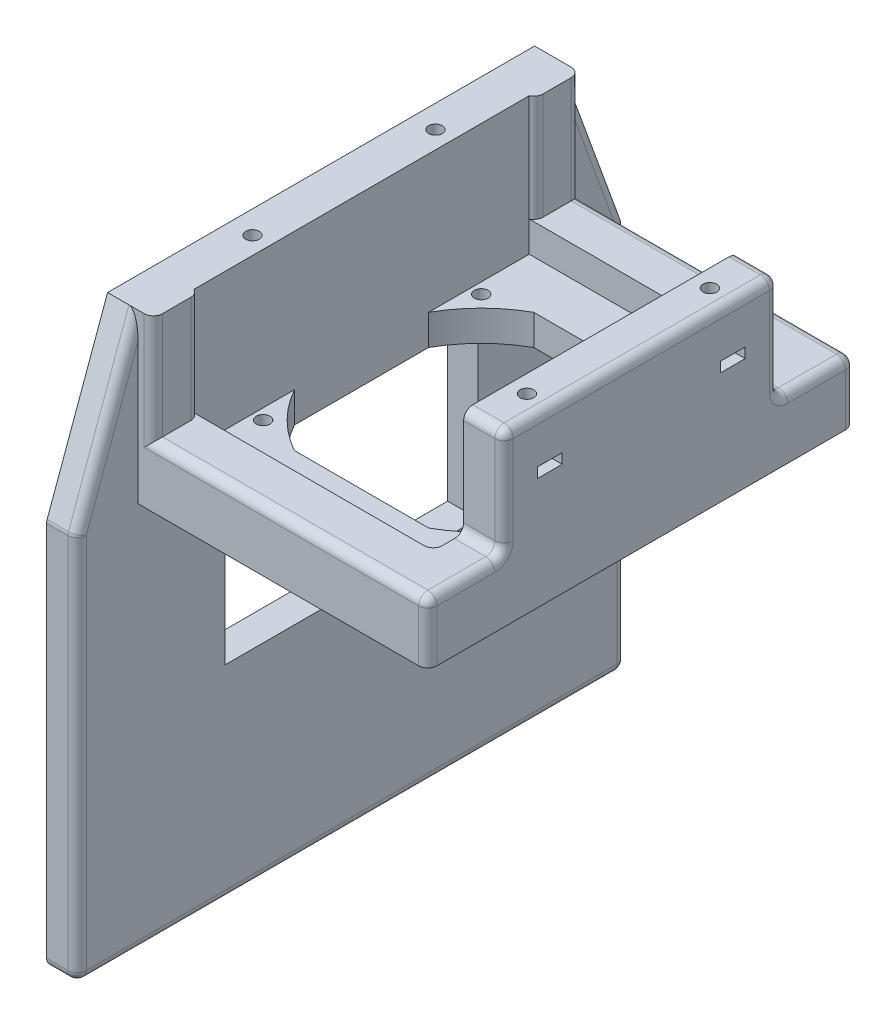
SolidWorks part; units mm, degrees
ref_plane "Front Plane" through (0, 0, 0) normal (0, 0, 1) x (1, 0, 0)
ref_plane "Top Plane" through (0, 0, 0) normal (0, 1, 0) x (1, 0, 0)
ref_plane "Right Plane" through (0, 0, 0) normal (1, 0, 0) x (0, 0, -1)
sketch "Sketch1" plane through (0, 0, 0) normal (0, 1, 0) x (1, 0, 0)
  line L9 (0, 0) -> (190, 0)
  line L10 (0, 0) -> (0, 140)
  line L11 (0, 140) -> (190, 140)
  line L12 (190, 0) -> (190, 140)
  dimension "D1" = 190
  dimension "D2" = 140
extrude "Boss-Extrude1" add sketch "Sketch1" along normal blind 10
sketch "Sketch3" plane through (0, 10, 0) normal (0, 1, 0) x (1, 0, 0)
  line L1 (42.5, 25) -> (57.5, 25)
  line L2 (42.5, 25) -> (42.5, 115)
  line L3 (42.5, 115) -> (57.5, 115)
  line L4 (57.5, 25) -> (57.5, 115)
  line L5 (42.5, 25) -> (57.5, 115) construction
  line L6 (42.5, 115) -> (57.5, 25) construction
  line L7 (0, 70) -> (190, 70) construction
  line L8 (0, 140) -> (0, 0) construction
  line L9 (190, 0) -> (190, 140) construction
  line L10 (95, 140) -> (95, 0) construction
  line L11 (190, 140) -> (0, 140) construction
  line L12 (0, 0) -> (190, 0) construction
  line L13 (147.5, 115) -> (132.5, 115)
  line L14 (132.5, 25) -> (132.5, 115)
  line L15 (147.5, 25) -> (132.5, 25)
  line L16 (147.5, 25) -> (147.5, 115)
  line L17 (132.5, 115) -> (147.5, 25) construction
  line L18 (147.5, 115) -> (132.5, 25) construction
  point P0 (50, 70)
  dimension "D1" = 45
  dimension "D2" = 75
  dimension "D3" = 90
extrude "Boss-Extrude3" add sketch "Sketch3" along normal blind 35
sketch "Sketch4" plane through (0, 45, 0) normal (0, 1, 0) x (1, 0, 0)
  line L0 (42.5, 70) -> (147.5, 70) construction
  line L1 (42.5, 115) -> (42.5, 25) construction
  line L2 (147.5, 25) -> (147.5, 115) construction
  line L3 (50, 100) -> (50, 70) construction
  line L4 (50, 115) -> (50, 100) construction
  line L5 (57.5, 115) -> (42.5, 115) construction
  circle A0 centre (50, 100) radius 2.25
  circle A1 centre (140, 100) radius 2.25
  circle A2 centre (140, 40) radius 2.25
  circle A3 centre (50, 40) radius 2.25
  dimension "D1" = 4.5
  dimension "D4" = 30
  dimension "D2" = 2
  dimension "D3" = 2
extrude "Cut-Extrude1" cut sketch "Sketch4" against normal blind 20
sketch "Sketch5" plane through (0, 10, 0) normal (0, 1, 0) x (1, 0, 0)
  line L0 (57.5, 25) -> (57.5, 115) construction
  line L1 (57.5, 125) -> (132.5, 125)
  line L2 (57.5, 125) -> (57.5, 15)
  line L3 (57.5, 15) -> (132.5, 15)
  line L4 (132.5, 125) -> (132.5, 15)
  line L5 (132.5, 115) -> (132.5, 25) construction
  line L6 (57.5, 25) -> (57.5, 115) construction
  line L8 (57.5, 70) -> (42.5, 70) construction
  line L10 (42.5, 115) -> (42.5, 25) construction
  dimension "D1" = 110
extrude "Cut-Extrude2" cut sketch "Sketch5" against normal blind 50
sketch "Sketch6" plane through (0, 0, 0) normal (0, -1, 0) x (-1, 0, 0)
  circle A0 centre (-50, 40) radius 4.5
  circle A1 centre (-140, 40) radius 4.5
  circle A2 centre (-140, 100) radius 4.5
  circle A3 centre (-50, 100) radius 4.5
  dimension "D1" = 2
  dimension "D2" = 2
extrude "Cut-Extrude3" [suppressed] cut sketch "Sketch6" against normal blind 10
sketch "Sketch8" plane through (0, 10, 0) normal (0, 1, 0) x (1, 0, 0)
  line L0 (10, 130) -> (10, 140) construction
  line L1 (190, 140) -> (0, 140) construction
  line L2 (10, 130) -> (0, 130) construction
  line L3 (0, 140) -> (0, 0) construction
  line L4 (190, 0) -> (190, 140) construction
  line L5 (0, 0) -> (190, 0) construction
  circle A0 centre (10, 130) radius 2.5
  circle A1 centre (180, 130) radius 2.5
  circle A2 centre (180, 10) radius 2.5
  circle A3 centre (10, 10) radius 2.5
  dimension "D1" = 10
  dimension "D2" = 10
  dimension "D5" = 10
  dimension "D6" = 10
  dimension "D3" = 2
  dimension "D4" = 2
extrude "Cut-Extrude4" cut sketch "Sketch8" against normal blind 10 contours A0
ref_plane "Plane1" through (0, 30, 0) normal (0, 1, 0) x (1, 0, 0)
sketch "Sketch10" plane through (0, 30, 0) normal (0, 1, 0) x (1, 0, 0)
  line L0 (45.95, 44.05) -> (42.5, 44.05)
  line L1 (54.05, 35.95) -> (45.95, 35.95)
  line L2 (54.05, 35.95) -> (54.05, 44.05)
  line L3 (54.05, 44.05) -> (45.95, 44.05)
  line L5 (54.05, 35.95) -> (45.95, 44.05) construction
  line L6 (54.05, 44.05) -> (45.95, 35.95) construction
  line L7 (42.5, 115) -> (42.5, 25) construction
  line L8 (42.5, 44.05) -> (42.5, 35.95)
  line L9 (42.5, 35.95) -> (45.95, 35.95)
  line L10 (42.5, 95.95) -> (45.95, 95.95)
  line L11 (54.05, 95.95) -> (45.95, 95.95)
  line L12 (54.05, 95.95) -> (54.05, 104.05)
  line L13 (54.05, 104.05) -> (45.95, 104.05)
  line L14 (45.95, 104.05) -> (42.5, 104.05)
  line L15 (42.5, 104.05) -> (42.5, 95.95)
  line L19 (95, 125) -> (95, 29.9699) construction
  line L20 (135.95, 44.05) -> (144.05, 35.95) construction
  line L21 (135.95, 35.95) -> (144.05, 44.05) construction
  line L22 (147.5, 35.95) -> (144.05, 35.95)
  line L23 (147.5, 44.05) -> (147.5, 35.95)
  line L24 (135.95, 44.05) -> (144.05, 44.05)
  line L25 (135.95, 35.95) -> (135.95, 44.05)
  line L26 (135.95, 35.95) -> (144.05, 35.95)
  line L27 (144.05, 44.05) -> (147.5, 44.05)
  line L28 (147.5, 104.05) -> (147.5, 95.95)
  line L29 (144.05, 104.05) -> (147.5, 104.05)
  line L30 (135.95, 104.05) -> (144.05, 104.05)
  line L31 (135.95, 95.95) -> (135.95, 104.05)
  line L32 (135.95, 95.95) -> (144.05, 95.95)
  line L33 (147.5, 95.95) -> (144.05, 95.95)
  point P0 (50, 40)
  point P32 (140, 40)
  dimension "D1" = 8.1
  dimension "D2" = 8.1
  dimension "D3" = 2
extrude "Cut-Extrude5" cut sketch "Sketch10" against normal blind 3.3
sketch "Sketch11" plane through (0, 10, 0) normal (0, 1, 0) x (1, 0, 0)
  line L0 (190, 140) -> (0, 140) construction
  line L1 (147.5, 140) -> (190, 140)
  line L2 (147.5, 140) -> (147.5, 0)
  line L3 (147.5, 0) -> (190, 0)
  line L4 (190, 140) -> (190, 0)
  line L5 (147.5, 25) -> (147.5, 115) construction
  line L6 (95, 125) -> (95, 15) construction
  line L7 (132.5, 125) -> (57.5, 125) construction
  line L8 (57.5, 15) -> (132.5, 15) construction
  line L9 (42.5, 0) -> (0, 0)
  line L10 (0, 140) -> (0, 0)
  line L11 (42.5, 140) -> (0, 140)
  line L12 (42.5, 140) -> (42.5, 0)
  point P15 (95, 35)
extrude "Cut-Extrude6" cut sketch "Sketch11" against normal blind 10
sketch "Sketch12" plane through (0, 10, 0) normal (0, 1, 0) x (1, 0, 0)
  line L0 (42.5, 0) -> (147.5, 0) construction
  line L1 (42.5, 140) -> (57.5, 140)
  line L2 (42.5, 140) -> (42.5, 115)
  line L3 (42.5, 115) -> (57.5, 115)
  line L4 (57.5, 140) -> (57.5, 115)
  line L5 (42.5, 25) -> (57.5, 25)
  line L6 (42.5, 25) -> (42.5, 0)
  line L7 (42.5, 0) -> (57.5, 0)
  line L8 (57.5, 25) -> (57.5, 0)
extrude "Boss-Extrude4" add sketch "Sketch12" along normal up to surface (35 mm away) up to face at (50, 45, -37.75)
sketch "Sketch14" plane through (0, 0, 0) normal (0, -1, 0) x (1, 0, 0)
  line L4 (147.5, -140) -> (147.5, 0)
  line L5 (147.5, 0) -> (42.5, 0)
  line L6 (42.5, 0) -> (42.5, -140)
  line L7 (42.5, -140) -> (147.5, -140)
  line L8 (147.5, -140) -> (147.5, 0)
  line L9 (147.5, 0) -> (42.5, 0)
  line L10 (42.5, 0) -> (42.5, -140)
  line L11 (42.5, -140) -> (147.5, -140)
  dimension "D1" = 0
extrude "Boss-Extrude5" add sketch "Sketch14" along normal blind 10
sketch "Sketch15" plane through (0, -10, 0) normal (0, -1, 0) x (1, 0, 0)
  line L0 (59.25, -34.25) -> (130.75, -34.25) construction
  line L1 (130.75, -34.25) -> (130.75, -105.75) construction
  line L2 (59.25, -34.25) -> (59.25, -105.75) construction
  line L3 (59.25, -105.75) -> (130.75, -105.75) construction
  line L4 (95, 0) -> (95, -34.25) construction
  line L5 (147.5, 0) -> (42.5, 0) construction
  line L6 (42.5, -70) -> (59.25, -70) construction
  line L7 (42.5, 0) -> (42.5, -140) construction
  line L8 (59.25, -34.25) -> (130.75, -105.75) construction
  line L9 (130.75, -34.25) -> (59.25, -105.75) construction
  line L10 (72.9901, -30.75) -> (117.0099, -30.75)
  line L11 (134.25, -47.9901) -> (134.25, -92.0099)
  line L12 (72.9901, -109.25) -> (134.25, -109.25)
  line L13 (55.75, -47.9901) -> (55.75, -92.0099)
  line L14 (55.75, -30.75) -> (134.25, -30.75) construction
  line L15 (55.75, -30.75) -> (55.75, -109.25) construction
  line L16 (134.25, -30.75) -> (134.25, -109.25) construction
  line L17 (55.75, -109.25) -> (134.25, -109.25) construction
  arc A0 (72.9901, -30.75) -> (55.75, -47.9901) centre (95, -70) ccw
  circle A1 centre (59.25, -34.25) radius 2.25
  circle A2 centre (130.75, -34.25) radius 2.25
  circle A3 centre (130.75, -105.75) radius 2.25
  circle A4 centre (59.25, -105.75) radius 2.25
  arc A5 (134.25, -47.9901) -> (117.0099, -30.75) centre (95, -70) ccw
  arc A6 (117.0099, -109.25) -> (134.25, -92.0099) centre (95, -70) ccw
  arc A7 (55.75, -92.0099) -> (72.9901, -109.25) centre (95, -70) ccw
  dimension "D3" = 2
  dimension "D1" = 71.5
  dimension "D2" = 3.5
  dimension "D4" = 2
extrude "Cut-Extrude7" cut sketch "Sketch15" against normal blind 10 contours L13 A7 L12 A6 L11 A5 L10 A0 | A2 | A1 | A4 | A3
sketch "Sketch16" plane through (0, 45, 0) normal (0, 1, 0) x (1, 0, 0)
  line L0 (55.75, 47.9901) -> (55.75, 92.0099) construction
  line L1 (55.75, 47.9901) -> (55.75, 92.0099)
  line L2 (134.25, 47.9901) -> (134.25, 92.0099) construction
  line L3 (134.25, 47.9901) -> (134.25, 92.0099)
  line L5 (57.5, 125) -> (55.75, 125)
  line L6 (57.5, 125) -> (57.5, 15)
  line L7 (57.5, 15) -> (55.75, 15)
  line L8 (55.75, 125) -> (55.75, 15)
  line L9 (147.5, 115) -> (132.5, 115) construction
  line L10 (132.5, 115) -> (134.25, 115)
  line L11 (132.5, 115) -> (132.5, 25)
  line L12 (132.5, 25) -> (134.25, 25)
  line L13 (134.25, 115) -> (134.25, 25)
  line L14 (132.5, 115) -> (132.5, 25) construction
  line L15 (132.5, 25) -> (147.5, 25) construction
  line L16 (132.5, 15) -> (57.5, 15) construction
  line L17 (132.5, 125) -> (57.5, 125) construction
  point P21 (0, 0)
  line M4 (147.5, 115) -> (132.5, 115)
  line M5 (132.5, 115) -> (132.5, 25)
  line M6 (132.5, 25) -> (147.5, 25)
extrude "Cut-Extrude8" cut sketch "Sketch16" along direction (0, -1, 0) on the side against the normal up to surface (45 mm away) contours L5 L8 L1 L7 L6 | L13 L3 M4 M5 M6
sketch "Sketch20" plane through (0, -10, 0) normal (0, -1, 0) x (1, 0, 0)
  line L1 (42.5, 20) -> (52.5, 20)
  line L2 (42.5, 20) -> (42.5, -160)
  line L3 (42.5, -160) -> (52.5, -160)
  line L4 (52.5, 20) -> (52.5, -160)
  line L5 (52.5, -70) -> (42.5, -70) construction
  line L6 (42.5, 0) -> (42.5, -140) construction
  dimension "D1" = 10
  dimension "D2" = 180
extrude "Boss-Extrude6" add sketch "Sketch20" along normal blind 127
sketch "Sketch21" plane through (52.5, 0, 0) normal (1, 0, 0) x (0, 0, -1)
  line L0 (140, -10) -> (0, -10) construction
  line L1 (28.5, -10) -> (111.5, -10)
  line L2 (28.5, -10) -> (28.5, -70)
  line L3 (28.5, -70) -> (111.5, -70)
  line L4 (111.5, -10) -> (111.5, -70)
  point P6 (70, -10)
  dimension "D1" = 60
  dimension "D2" = 83
extrude "Cut-Extrude10" cut sketch "Sketch21" against normal blind 76.2
sketch "Sketch22" plane through (52.5, 0, 0) normal (1, 0, 0) x (0, 0, -1)
  line L0 (0, 45) -> (-20, -10)
  line L1 (-20, -10) -> (0, -10)
  line L2 (0, -10) -> (-20, -10) construction
  line L3 (0, -10) -> (0, 45)
  line L4 (140, 45) -> (160, -10)
  line L5 (160, -10) -> (140, -10)
  line L6 (140, -10) -> (140, 45)
extrude "Boss-Extrude7" add sketch "Sketch22" against normal up to surface (10 mm away) up to face at (42.5, -40, -70)
sketch "Sketch17" plane through (0, 10, 0) normal (0, 1, 0) x (1, 0, 0)
  line L1 (132.5, 125) -> (134.25, 125)
  line L2 (132.5, 125) -> (132.5, 115)
  line L3 (132.5, 115) -> (134.25, 115)
  line L4 (134.25, 125) -> (134.25, 115)
  line L5 (132.5, 25) -> (134.25, 25)
  line L6 (132.5, 25) -> (132.5, 15)
  line L7 (132.5, 15) -> (134.25, 15)
  line L8 (134.25, 25) -> (134.25, 15)
extrude "Cut-Extrude9" cut sketch "Sketch17" against normal up to surface (10 mm away) contours L8 L5 L6 L7 | L2 L1 L4 L3 up to face at (59.25, 0, -108)
fillet "Fillet1" radius 3 30 edges at (102.5, 10, -140) (147.5, 10, -127.5) (147.5, 10, -12.5) (147.5, 0, 0) (147.5, 0, -140) (57.5, 27.5, -140) (102.5, 10, 0) (57.5, 27.5, 0) (147.5, 27.5, -25) (140.875, 10, -115) (147.5, 27.5, -115) (147.5, 45, -70) (140.875, 45, -115) (140.875, 45, -25) (140.875, 10, -25) (56.625, 45, -125) (57.5, 27.5, -15) (56.625, 45, -15) (57.5, 27.5, -125) (47.5, -10, -160) (52.5, -73.5, -160) (47.5, -10, 20) (52.5, -73.5, 20) (47.5, -137, -160) (52.5, -137, -70) (47.5, -137, 20) (52.5, 17.5, 10) (52.5, 17.5, -150) (134.25, 5, -15) (134.25, 5, -125)
